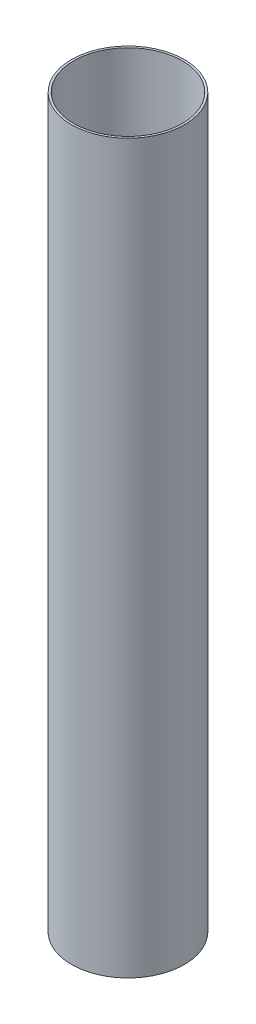
SolidWorks part; units mm, degrees
ref_plane "Front Plane" through (0, 0, 0) normal (0, 0, 1) x (1, 0, 0)
ref_plane "Top Plane" through (0, 0, 0) normal (0, 1, 0) x (1, 0, 0)
ref_plane "Right Plane" through (0, 0, 0) normal (1, 0, 0) x (0, 0, -1)
sketch "Sketch1" plane through (0, 0, 0) normal (0, 1, 0) x (1, 0, 0)
  circle A0 centre (0, 0) radius 39.6
  circle A1 centre (0, 0) radius 38.1
  dimension "D1" = 79.2
  dimension "D2" = 76.2
extrude "Boss-Extrude1" add sketch "Sketch1" along normal blind 510
